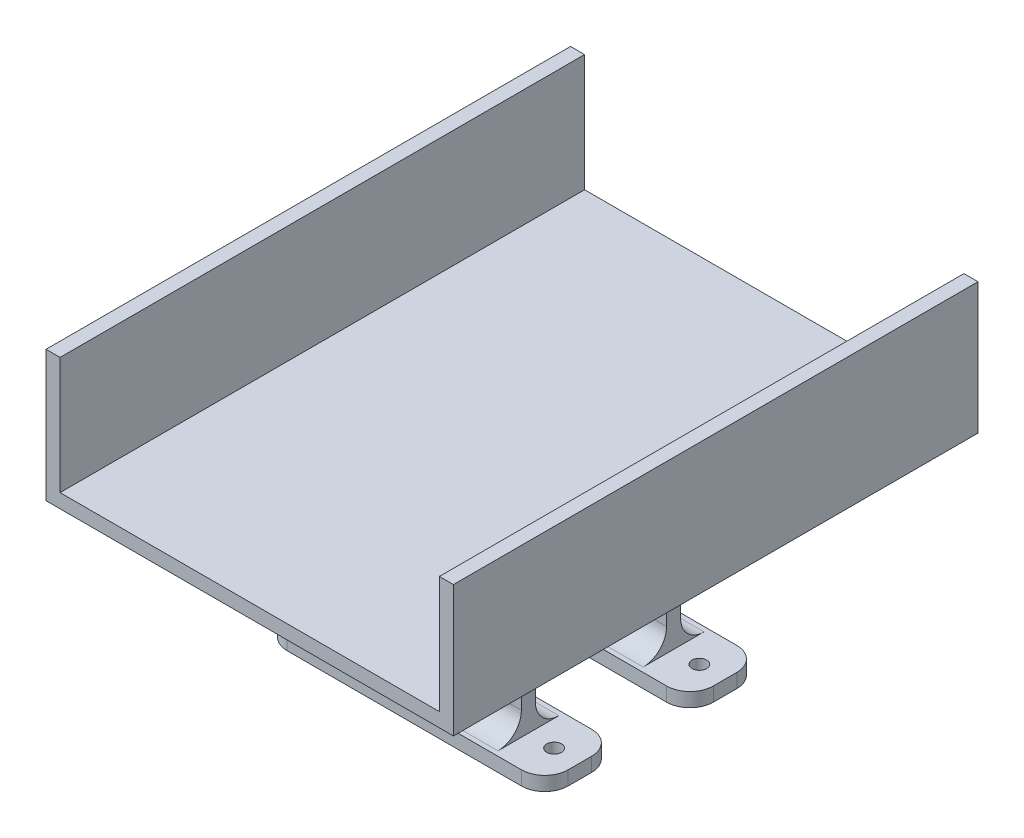
SolidWorks part; units mm, degrees
material "Du"
ref_plane "Front Plane" through (0, 0, 0) normal (0, 0, 1) x (1, 0, 0)
ref_plane "Top Plane" through (0, 0, 0) normal (0, 1, 0) x (1, 0, 0)
ref_plane "Right Plane" through (0, 0, 0) normal (1, 0, 0) x (0, 0, -1)
sketch "Sketch1" plane through (0, 0, 0) normal (0, 1, 0) x (1, 0, 0)
  line L1 (-43.5, -56) -> (43.5, -56)
  line L2 (-43.5, -56) -> (-43.5, 56)
  line L3 (-43.5, 56) -> (43.5, 56)
  line L4 (43.5, -56) -> (43.5, 56)
  line L5 (-43.5, -56) -> (43.5, 56) construction
  line L6 (-43.5, 56) -> (43.5, -56) construction
  point P0 (0, 0)
  dimension "D1" = 112
  dimension "D2" = 87
extrude "Boss-Extrude1" add sketch "Sketch1" along normal blind 3
sketch "Sketch2" plane through (0, 0, 0) normal (0, -1, 0) x (1, 0, 0)
  line L0 (0, 56) -> (0, -56) construction
  line L1 (-43.5, 56) -> (43.5, 56) construction
  line L2 (43.5, -56) -> (-43.5, -56) construction
  line L3 (-43.5, 0) -> (43.5, 0) construction
  line L4 (-43.5, -56) -> (-43.5, 56) construction
  line L5 (43.5, 56) -> (43.5, -56) construction
  line L6 (19, -14) -> (19, -17)
  line L7 (19, 14) -> (-19, 14)
  line L8 (19, 14) -> (19, 17)
  line L9 (19, 17) -> (-19, 17)
  line L10 (-19, 14) -> (-19, 17)
  line L11 (19, 14) -> (-19, 17) construction
  line L12 (19, 17) -> (-19, 14) construction
  line L13 (19, -14) -> (-19, -17) construction
  line L14 (19, -17) -> (-19, -14) construction
  line L15 (19, -14) -> (-19, -14)
  line L16 (-19, -14) -> (-19, -17)
  line L17 (19, -17) -> (-19, -17)
  point P12 (0, 15.5)
  point P21 (0, -15.5)
  dimension "D1" = 3
  dimension "D2" = 38
  dimension "D3" = 31
extrude "Boss-Extrude2" add sketch "Sketch2" along normal blind 32
sketch "Sketch8" plane through (0, -32, 0) normal (0, -1, 0) x (1, 0, 0)
  line L0 (19, -14) -> (-19, -14) construction
  line L1 (-19, -14) -> (-19, -17) construction
  line L2 (-19, -17) -> (19, -17) construction
  line L3 (19, -17) -> (19, -14) construction
  line L4 (-19, 17) -> (-19, 14) construction
  line L5 (-19, 14) -> (19, 14) construction
  line L6 (19, 14) -> (19, 17) construction
  line L7 (19, 17) -> (-19, 17) construction
  line L8 (19, -14) -> (-19, -14)
  line L9 (-19, -14) -> (-19, -17)
  line L10 (-19, -17) -> (19, -17)
  line L11 (19, -17) -> (19, -14)
  line L12 (-19, 17) -> (-19, 14)
  line L13 (-19, 14) -> (19, 14)
  line L14 (19, 14) -> (19, 17)
  line L15 (19, 17) -> (-19, 17)
  line L16 (0, 17) -> (0, -17) construction
  line L17 (-19, 15.5) -> (19, 15.5) construction
  line L18 (-19, -15.5) -> (19, -15.5) construction
  line L20 (30, 8) -> (-30, 8)
  line L21 (30, 8) -> (30, 23)
  line L22 (30, 23) -> (-30, 23)
  line L23 (-30, 8) -> (-30, 23)
  line L24 (30, 8) -> (-30, 23) construction
  line L25 (30, 23) -> (-30, 8) construction
  line L26 (30, -23) -> (-30, -23)
  line L27 (30, -23) -> (30, -8)
  line L28 (30, -8) -> (-30, -8)
  line L29 (-30, -23) -> (-30, -8)
  line L30 (30, -23) -> (-30, -8) construction
  line L31 (30, -8) -> (-30, -23) construction
  circle A0 centre (-24.5, 15.5) radius 1.575
  circle A1 centre (24.5, 15.5) radius 1.575
  circle A2 centre (-24.5, -15.5) radius 1.575
  circle A3 centre (24.5, -15.5) radius 1.575
  point P14 (0, 15.5)
  point P19 (0, -15.5)
  dimension "D5" = 3.15
  dimension "D7" = 3.15
  dimension "D1" = 15
  dimension "D2" = 60
  dimension "D3" = 15
  dimension "D4" = 60
  dimension "D6" = 5.5
  dimension "D8" = 5.5
extrude "Boss-Extrude5" add sketch "Sketch8" along normal blind 3 separate body
sketch "Sketch9" plane through (0, 0, 14) normal (0, 0, 1) x (1, 0, 0)
  line L4 (19, -32) -> (-19, -32)
  line L5 (-19, -32) -> (-19, -35)
  line L6 (-19, -35) -> (19, -35)
  line L7 (19, -35) -> (19, -32)
  line L8 (19, -32) -> (-19, -32)
  line L9 (-19, -32) -> (-19, -35)
  line L10 (-19, -35) -> (19, -35)
  line L11 (19, -35) -> (19, -32)
  dimension "D1" = 0
extrude "Boss-Extrude6" add sketch "Sketch9" along normal blind 3
sketch "Sketch10" plane through (0, 0, -14) normal (0, 0, -1) x (-1, 0, 0)
  line L4 (19, -32) -> (-19, -32)
  line L5 (-19, -32) -> (-19, -35)
  line L6 (-19, -35) -> (19, -35)
  line L7 (19, -35) -> (19, -32)
  line L8 (19, -32) -> (-19, -32)
  line L9 (-19, -32) -> (-19, -35)
  line L10 (-19, -35) -> (19, -35)
  line L11 (19, -35) -> (19, -32)
  dimension "D1" = 0
extrude "Boss-Extrude7" add sketch "Sketch10" along normal blind 3
fillet "Fillet2" radius 5 4 edges at (30, -33.5, -8) (-30, -33.5, -8) (30, -33.5, -23) (-30, -33.5, -23)
fillet "Fillet3" radius 5 4 edges at (-30, -33.5, 23) (30, -33.5, 23) (-30, -33.5, 8) (30, -33.5, 8)
fillet "Fillet4" radius 5 8 edges at (0, 0, 14) (0, 0, 17) (0, 0, -14) (0, 0, -17) (0, -32, 17) (0, -32, 14) (0, -32, -14) (0, -32, -17)
sketch "Sketch12" plane through (0, 3, 0) normal (0, 1, 0) x (1, 0, 0)
  line L0 (0, -56) -> (0, 56) construction
  line L1 (43.5, 56) -> (43.5, -56)
  line L2 (-43.5, 56) -> (-40.5, 56)
  line L3 (-43.5, 56) -> (-43.5, -56)
  line L4 (43.5, -56) -> (43.5, 56)
  line L5 (43.5, 56) -> (-43.5, 56)
  line L6 (-43.5, 56) -> (-43.5, -56)
  line L7 (-43.5, -56) -> (43.5, -56)
  line L8 (43.5, -56) -> (43.5, 56)
  line L9 (43.5, 56) -> (-43.5, 56)
  line L10 (-43.5, 56) -> (-43.5, -56)
  line L11 (-43.5, -56) -> (43.5, -56)
  line L12 (-43.5, -56) -> (-40.5, -56)
  line L13 (-40.5, 56) -> (-40.5, -56)
  line L14 (-42, -56) -> (-42, 56) construction
  line L15 (-43.5, 0) -> (-40.5, 0) construction
  line L16 (42, -56) -> (42, 56) construction
  line L17 (43.5, 0) -> (40.5, 0) construction
  line L18 (43.5, 56) -> (40.5, 56)
  line L19 (40.5, 56) -> (40.5, -56)
  line L20 (43.5, -56) -> (40.5, -56)
  point P82 (-42, 0)
  point P83 (42, 0)
  point P84 (43.5, 0)
  point P85 (42, 56)
  point P86 (40.5, 0)
  point P87 (42, -56)
  dimension "D2" = 3
  dimension "D3" = 112
  dimension "D1" = 0
extrude "Boss-Extrude8" add sketch "Sketch12" along normal blind 25 contours L3 L12 L13 L2 | L19 L20 L1 L18
